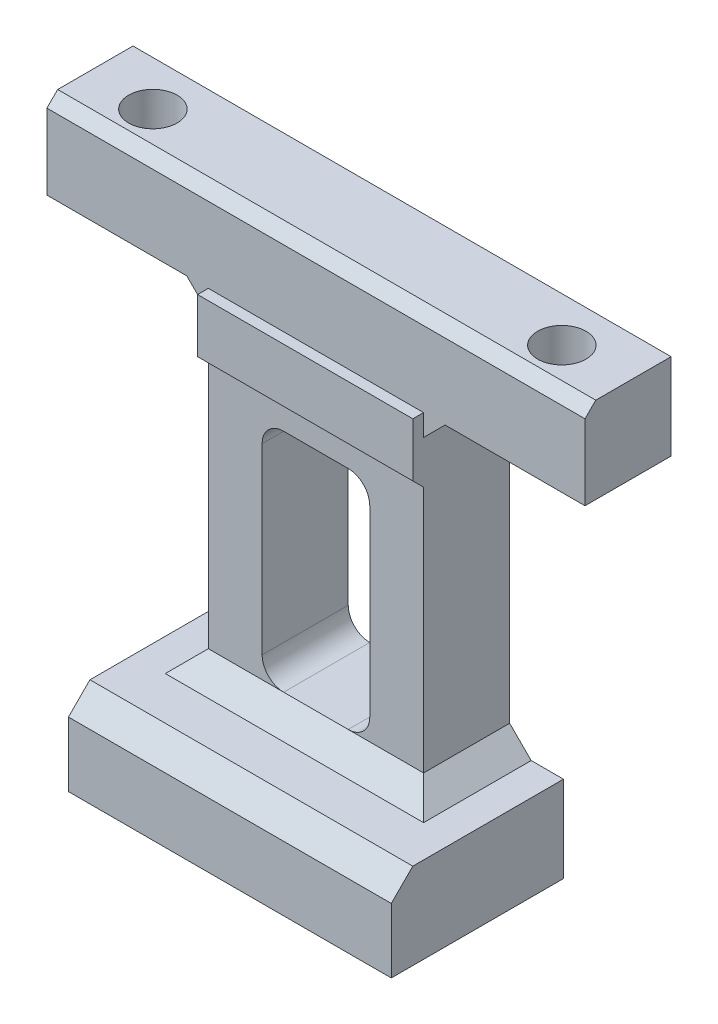
SolidWorks part; units mm, degrees
ref_plane "正面" through (0, 0, 0) normal (0, 0, 1) x (1, 0, 0)
ref_plane "平面" through (0, 0, 0) normal (0, 1, 0) x (1, 0, 0)
ref_plane "右側面" through (0, 0, 0) normal (1, 0, 0) x (0, 0, -1)
sketch "ｽｹｯﾁ1" plane through (0, 0, 0) normal (0, 0, 1) x (1, 0, 0)
  line L0 (0, 0) -> (0, 47) construction
  line L1 (0, 0) -> (10, 0)
  line L2 (10, 0) -> (10, 5)
  line L3 (10, 5) -> (-10, 5)
  line L4 (-10, 5) -> (-10, 0)
  line L5 (-10, 0) -> (0, 0)
  line L6 (0, 5) -> (10, 5)
  line L7 (10, 5) -> (10, 39)
  line L8 (10, 39) -> (-10, 39)
  line L9 (-10, 39) -> (-10, 5)
  line L10 (-10, 5) -> (0, 5)
  line L11 (-25, 39) -> (25, 39)
  line L12 (25, 39) -> (25, 47)
  line L13 (25, 47) -> (-25, 47)
  line L14 (-25, 47) -> (-25, 39)
  line L16 (-10, 39) -> (10, 39)
  line L17 (-10, 39) -> (10, 39)
  line L18 (-10, 39) -> (-10, 33)
  line L19 (-10, 33) -> (10, 33)
  line L20 (10, 39) -> (10, 33)
  dimension "D1" = 10
  dimension "D2" = 10
  dimension "D3" = 5
  dimension "D4" = 10
  dimension "D5" = 10
  dimension "D6" = 25
  dimension "D7" = 25
  dimension "D8" = 39
  dimension "D9" = 8
  dimension "D10" = 6
extrude "ﾎﾞｽ - 押し出し1" add sketch "ｽｹｯﾁ1" against normal blind 8 contours L11 L12 L13 L14 | L10 L6 L7 L8 L9 | L5 L1 L2 L3 L4
sketch "ｽｹｯﾁ3" plane through (0, 0, 0) normal (0, 0, 1) x (1, 0, 0)
  line L0 (10, 0) -> (10, 39) construction
  line L1 (-10, 39) -> (10, 39)
  line L2 (-10, 39) -> (-10, 35)
  line L3 (-10, 35) -> (10, 35)
  line L4 (10, 39) -> (10, 35)
  dimension "D1" = 4
extrude "ﾎﾞｽ - 押し出し2" add sketch "ｽｹｯﾁ3" along normal blind 1
sketch "ｽｹｯﾁ4" plane through (0, 47, 0) normal (0, 1, 0) x (1, 0, 0)
  circle A0 centre (19, 3.8474) radius 2.25
  circle A1 centre (-19, 3.8474) radius 2.25
  dimension "D3" = 4.5
  dimension "D1" = 19
  dimension "D2" = 19
extrude "ｶｯﾄ - 押し出し3" cut sketch "ｽｹｯﾁ4" against normal blind 10
chamfer "面取り2" distance 1 angle 45 1 edges at (0, 47, 0)
chamfer "面取り3" distance 2 angle 45 2 edges at (10, 39, -4) (-10, 39, -4)
chamfer "面取り4" distance 2 angle 45 1 edges at (0, 35, 0)
sketch "ｽｹｯﾁ6" plane through (0, 0, 0) normal (0, 0, 1) x (1, 0, 0)
  line L0 (-10, 33) -> (-10, 0) construction
  line L1 (-10, 0) -> (10, 0)
  line L2 (-10, 0) -> (-10, 8)
  line L3 (-10, 8) -> (10, 8)
  line L4 (10, 0) -> (10, 8)
  line L5 (10, 0) -> (10, 33) construction
  dimension "D1" = 8
extrude "ﾎﾞｽ - 押し出し3" add sketch "ｽｹｯﾁ6" along normal blind 8
sketch "ｽｹｯﾁ7" plane through (0, 0, 0) normal (0, 0, 1) x (1, 0, 0)
  line L0 (0, 8) -> (0, 33) construction
  line L1 (10, 8) -> (-10, 8) construction
  line L2 (10, 33) -> (-10, 33) construction
  line L4 (-5, 31) -> (5, 31)
  line L5 (-5, 31) -> (-5, 10)
  line L6 (-5, 10) -> (5, 10)
  line L7 (5, 31) -> (5, 10)
  line L8 (-5, 31) -> (5, 10) construction
  line L9 (-5, 10) -> (5, 31) construction
  point P6 (0, 20.5)
  dimension "D1" = 10
  dimension "D2" = 21
extrude "ｶｯﾄ - 押し出し4" cut sketch "ｽｹｯﾁ7" against normal through all
fillet "ﾌｨﾚｯﾄ1" radius 2 4 edges at (5, 10, -4) (5, 31, -4) (-5, 31, -4) (-5, 10, -4)
sketch "ｽｹｯﾁ8" plane through (0, 0, 0) normal (0, -1, 0) x (1, 0, 0)
  line L0 (0, 8) -> (0, -8) construction
  line L1 (-10, 8) -> (10, 8) construction
  line L2 (-10, -8) -> (10, -8) construction
  circle A0 centre (-6, 0) radius 2.4
  circle A1 centre (6, 0) radius 2.4
  dimension "D1" = 4.8
  dimension "D2" = 4.8
  dimension "D3" = 8
  dimension "D4" = 8
  dimension "D5" = 6
  dimension "D6" = 6
extrude "ｶｯﾄ - 押し出し5" cut sketch "ｽｹｯﾁ8" against normal blind 6
sketch "ｽｹｯﾁ9" plane through (0, 0, 8) normal (0, 0, 1) x (1, 0, 0)
  line L0 (-10, 0) -> (10, 0) construction
  line L1 (10, 0) -> (15, 0)
  line L2 (10, 0) -> (10, 8)
  line L3 (10, 8) -> (15, 8)
  line L4 (15, 0) -> (15, 8)
  line L5 (-10, 0) -> (-15, 0)
  line L6 (-10, 0) -> (-10, 8)
  line L7 (-10, 8) -> (-15, 8)
  line L8 (-15, 0) -> (-15, 8)
  line L9 (-10, 8) -> (-10, 0) construction
  line L10 (10, 8) -> (-10, 8) construction
  dimension "D1" = 5
  dimension "D2" = 5
extrude "ﾎﾞｽ - 押し出し4" add sketch "ｽｹｯﾁ9" against normal up to surface (16 mm away) up to face at (0, 20.5, -8)
chamfer "面取り5" distance 2 angle 45 1 edges at (0, 8, 8)
chamfer "面取り6" distance 2 angle 45 3 edges at (-10, 8, -4) (10, 8, -4) (0, 8, 0)
